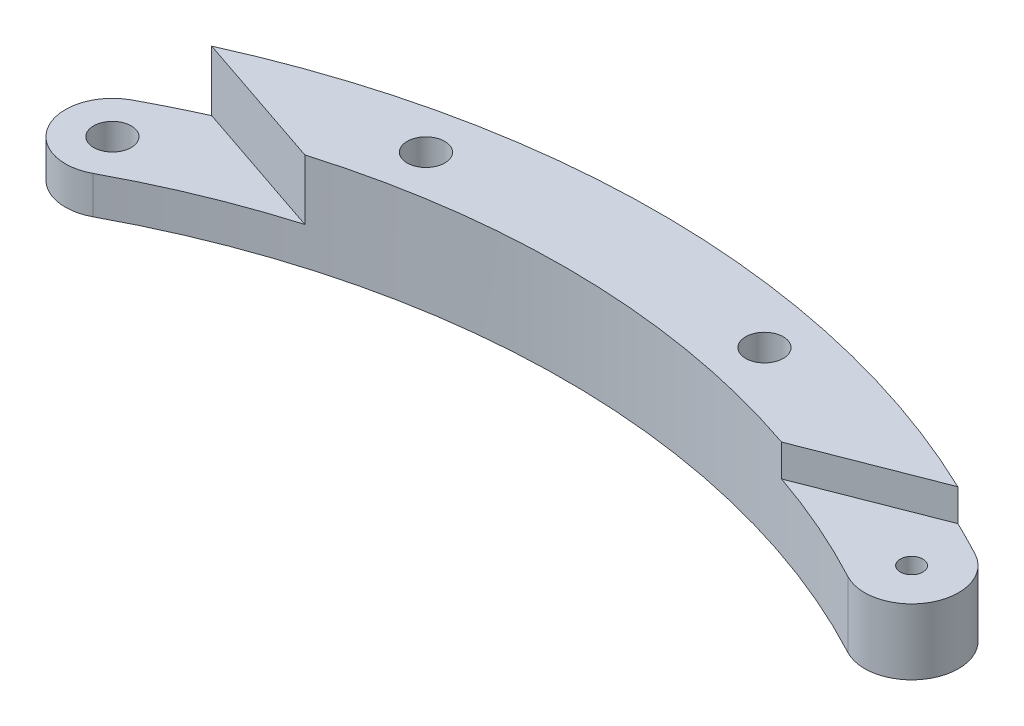
SolidWorks part; units mm, degrees
ref_plane "Front Plane" through (0, 0, 0) normal (0, 0, 1) x (1, 0, 0)
ref_plane "Top Plane" through (0, 0, 0) normal (0, 1, 0) x (1, 0, 0)
ref_plane "Right Plane" through (0, 0, 0) normal (1, 0, 0) x (0, 0, -1)
sketch "Sketch2" plane through (0, 0, 0) normal (0, 1, 0) x (1, 0, 0)
  arc A4 (0, 0) -> (42.5, 0) centre (21.25, -39.6666) cw construction
  arc A5 (1.1806, -2.2037) -> (41.3194, -2.2037) centre (21.25, -39.6666) cw
  arc A6 (-1.1806, 2.2037) -> (43.6806, 2.2037) centre (21.25, -39.6666) cw
  circle A7 centre (0, 0) radius 2.5
  circle A8 centre (42.5, 0) radius 2.5
  circle A9 centre (0, 0) radius 1
  circle A10 centre (42.5, 0) radius 0.6
  dimension "D1" = 2.5
  dimension "D3" = 45
  dimension "D4" = 42.5
  dimension "D5" = 1.2
  dimension "D6" = 2
  dimension "D2" = 2.5
extrude "Boss-Extrude2" add sketch "Sketch2" along normal blind 2 contours A8 A6 A7 A5 | A8 A10 | A7 A9 region at (21.25, 0, -3.8859) region at (-2.1414, 0, 1.1472) region at (40.3586, 0, -1.1472)
sketch "Sketch3" plane through (0, 2, 0) normal (0, 1, 0) x (1, 0, 0)
  line L0 (1.6703, 3.6103) -> (9.1577, 1.0768)
  line L1 (35.0535, 0.5293) -> (41.7986, 3.1587)
  arc A0 (41.3194, -2.2037) -> (1.1806, -2.2037) centre (21.25, -39.6666) ccw construction
  arc A1 (43.6806, 2.2037) -> (-1.1806, 2.2037) centre (21.25, -39.6666) ccw construction
  arc A10 (41.3194, -2.2037) -> (1.1806, -2.2037) centre (21.25, -39.6666) ccw
  arc A11 (41.3194, -2.2037) -> (43.6806, 2.2037) centre (42.5, 0) ccw
  arc A12 (43.6806, 2.2037) -> (-1.1806, 2.2037) centre (21.25, -39.6666) ccw
  arc A13 (-1.1806, 2.2037) -> (1.1806, -2.2037) centre (0, 0) ccw
  arc A14 (41.3194, -2.2037) -> (1.1806, -2.2037) centre (21.25, -39.6666) ccw
  arc A15 (41.3194, -2.2037) -> (43.6806, 2.2037) centre (42.5, 0) ccw
  arc A16 (43.6806, 2.2037) -> (-1.1806, 2.2037) centre (21.25, -39.6666) ccw
  arc A17 (-1.1806, 2.2037) -> (1.1806, -2.2037) centre (0, 0) ccw
  point P6 (10.7295, 1.5107)
  point P12 (41.7986, 3.1587)
  point P20 (0, 0)
  point P21 (9.0565, 1.0467)
  point P22 (1.405, 3.4892)
  point P23 (1.6703, 3.6103)
  point P24 (0, 0)
  point P25 (9.1577, 1.0768)
  arc M7 (1.1806, -2.2037) -> (41.3194, -2.2037) centre (21.25, -39.6666) cw
  arc M9 (43.6806, 2.2037) -> (-1.1806, 2.2037) centre (21.25, -39.6666) ccw
  dimension "D3" = 0
extrude "Boss-Extrude3" add sketch "Sketch3" along normal blind 3.2 contours M9 M7 region at (21.9209, 2, -4.4096)
sketch "Sketch4" plane through (0, 2, 0) normal (0, 1, 0) x (1, 0, 0)
  line L1 (41.7986, 3.1587) -> (35.0535, 0.5293)
  line L2 (41.7986, 3.1587) -> (35.0535, 0.5293)
  arc A3 (41.3194, -2.2037) -> (35.0535, 0.5293) centre (21.25, -39.6666) ccw
  arc A4 (41.3194, -2.2037) -> (43.6806, 2.2037) centre (42.5, 0) ccw
  arc A5 (43.6806, 2.2037) -> (41.7986, 3.1587) centre (21.25, -39.6666) ccw
  arc A6 (41.3194, -2.2037) -> (35.0535, 0.5293) centre (21.25, -39.6666) ccw
  arc A7 (41.3194, -2.2037) -> (43.6806, 2.2037) centre (42.5, 0) ccw
  arc A8 (43.6806, 2.2037) -> (41.7986, 3.1587) centre (21.25, -39.6666) ccw
  circle M9 centre (42.5, 0) radius 0.6
  dimension "D1" = 0
extrude "Boss-Extrude4" add sketch "Sketch4" along normal blind 1.5 contours M9 | L2 A6 A7 A8 region at (42.5, 2, 0)
sketch "Sketch5" plane through (0, 5.2, 0) normal (0, 1, 0) x (1, 0, 0)
  circle A0 centre (12.25, 4.4242) radius 1
  circle A1 centre (30.25, 4.4242) radius 1
  arc A7 (0, 0) -> (42.5, 0) centre (21.25, -39.6666) cw construction
  point P4 (0, 0)
  point P5 (31.3818, 4.178)
  point P6 (30.7945, 4.3096)
  dimension "D1" = 45
  dimension "D2" = 18
  dimension "D3" = 2
extrude "Cut-Extrude1" cut sketch "Sketch5" against normal through all
